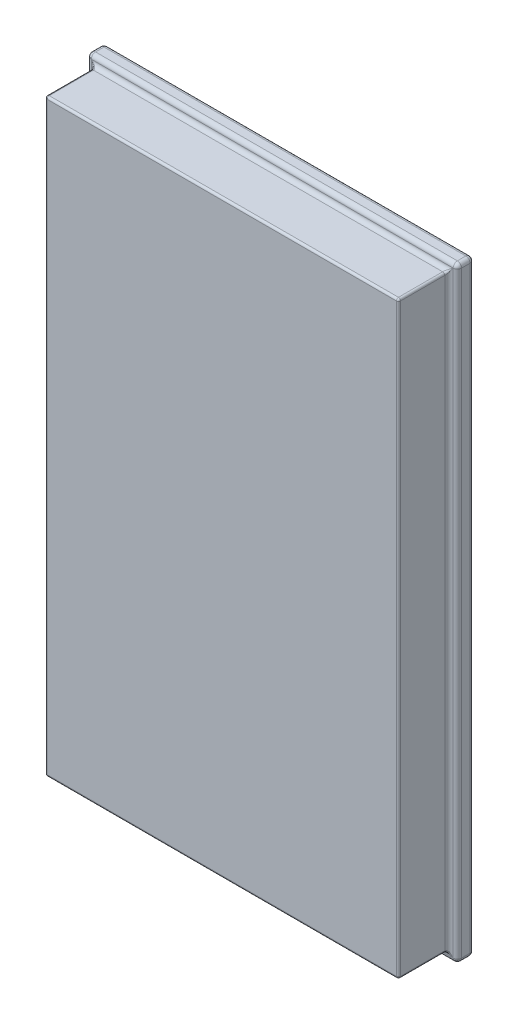
SolidWorks part; units mm, degrees
ref_plane "Front Plane" through (0, 0, 0) normal (1, 0, 0) x (0, 1, 0)
ref_plane "Top Plane" through (0, 0, 0) normal (0, 0, 1) x (0, 1, 0)
ref_plane "Right Plane" through (0, 0, 0) normal (0, 1, 0) x (-1, 0, 0)
sketch "Sketch1" plane through (0, 0, 0) normal (0, 0, 1) x (0, 1, 0)
  line L1 (-228.6, -139.7) -> (228.6, -139.7)
  line L2 (-228.6, -139.7) -> (-228.6, 139.7)
  line L3 (-228.6, 139.7) -> (228.6, 139.7)
  line L4 (228.6, -139.7) -> (228.6, 139.7)
  line L5 (-228.6, -139.7) -> (228.6, 139.7) construction
  line L6 (-228.6, 139.7) -> (228.6, -139.7) construction
extrude "Boss-Extrude1" add sketch "Sketch1" along normal blind 12.7
sketch "Sketch2" plane through (0, 0, 0) normal (0, 0, 1) x (0, 1, 0)
  line L1 (-222.25, -133.35) -> (222.25, -133.35)
  line L2 (-222.25, -133.35) -> (-222.25, 133.35)
  line L3 (-222.25, 133.35) -> (222.25, 133.35)
  line L4 (222.25, -133.35) -> (222.25, 133.35)
  line L5 (-222.25, -133.35) -> (222.25, 133.35) construction
  line L6 (-222.25, 133.35) -> (222.25, -133.35) construction
extrude "Boss-Extrude2" add sketch "Sketch2" along normal blind 38.1 from offset 12.7
fillet "Fillet1" radius 3.175 16 edges at (-139.7, 228.6, 6.35) (-139.7, -228.6, 6.35) (139.7, -228.6, 6.35) (139.7, 228.6, 6.35) (-139.7, 0, 0) (0, -228.6, 0) (139.7, 0, 0) (0, 228.6, 0) (-133.35, 0, 12.7) (0, -222.25, 12.7) (133.35, 0, 12.7) (0, 222.25, 12.7) (139.7, 0, 12.7) (0, -228.6, 12.7) (-139.7, 0, 12.7) (0, 228.6, 12.7) tangent propagation no
fillet "Fillet2" radius 1.5875 8 edges at (-133.35, 222.25, 33.3375) (-133.35, -222.25, 33.3375) (133.35, 222.25, 33.3375) (133.35, -222.25, 33.3375) (133.35, 0, 50.8) (0, -222.25, 50.8) (-133.35, 0, 50.8) (0, 222.25, 50.8) tangent propagation no
